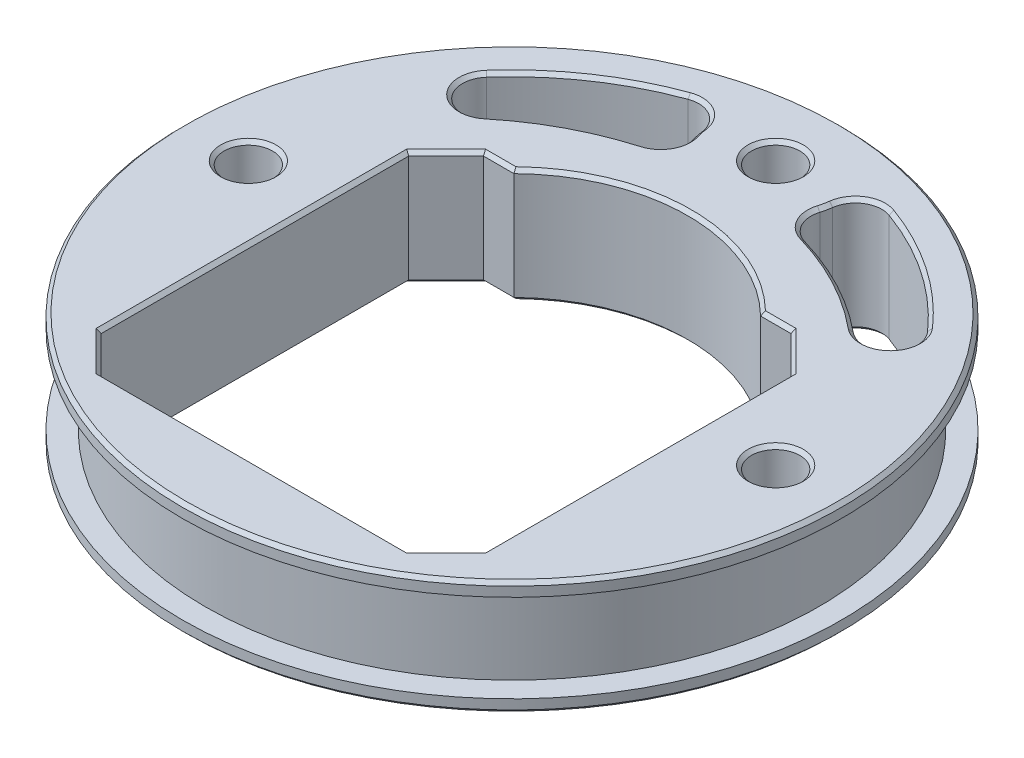
SolidWorks part; units mm, degrees
ref_plane "Front Plane" through (0, 0, 0) normal (0, 0, 1) x (1, 0, 0)
ref_plane "Top Plane" through (0, 0, 0) normal (0, 1, 0) x (1, 0, 0)
ref_plane "Right Plane" through (0, 0, 0) normal (1, 0, 0) x (0, 0, -1)
sketch "Sketch1" plane through (0, 0, 0) normal (0, 1, 0) x (1, 0, 0)
  line L0 (0, 0) -> (0, -7.5) construction
  line L1 (-17.4944, 14.25) -> (-14.0334, 14.25)
  line L2 (17.4944, 14.25) -> (21.75, 9.9944)
  line L3 (21.75, 9.9944) -> (21.75, -24.9944)
  line L4 (21.75, -24.9944) -> (17.4944, -29.25)
  line L5 (17.4944, -29.25) -> (-17.4944, -29.25)
  line L6 (-17.4944, -29.25) -> (-21.75, -24.9944)
  line L7 (-21.75, -24.9944) -> (-21.75, 9.9944)
  line L8 (-21.75, 9.9944) -> (-17.4944, 14.25)
  line L9 (14.0334, 14.25) -> (17.4944, 14.25)
  circle A0 centre (0, 0) radius 35 construction
  circle A1 centre (0, -7.5) radius 27.9127 construction
  circle A2 centre (0, 0) radius 30 construction
  circle A3 centre (0, 30) radius 2.75
  circle A4 centre (30, 0) radius 2.75
  circle A5 centre (-30, 0) radius 2.75
  circle A6 centre (0, 0) radius 37.5
  arc A7 (-20.9311, 17.8995) -> (20.9311, 17.8995) centre (0, -7.5) ccw construction
  arc A8 (7.1823, 27.8402) -> (7.4393, 29.0476) centre (0, 30) ccw
  arc A9 (6.9711, 32.7667) -> (-6.9711, 32.7667) centre (0, 0) ccw construction
  arc A10 (-25.0854, 22.203) -> (-20.9311, 17.8995) centre (-22.8389, 20.2147) ccw
  arc A11 (20.9311, 17.8995) -> (25.0854, 22.203) centre (22.8389, 20.2147) ccw
  arc A12 (-5.5389, 24.9433) -> (5.5389, 24.9433) centre (0, 30) ccw construction
  arc A13 (5.5389, 24.9433) -> (-5.5389, 24.9433) centre (0, -7.5) ccw construction
  arc A14 (-9.2152, 24.0963) -> (-20.9311, 17.8995) centre (0, -7.5) ccw
  arc A15 (20.9311, 17.8995) -> (9.2152, 24.0963) centre (0, -7.5) ccw
  arc A16 (25.0854, 22.203) -> (11.4394, 31.4863) centre (0, 0) ccw
  arc A17 (-11.4394, 31.4863) -> (-25.0854, 22.203) centre (0, 0) ccw
  arc A18 (-25.0854, 22.203) -> (25.0854, 22.203) centre (0, 0) ccw construction
  arc A19 (-7.4393, 29.0476) -> (-7.1823, 27.8402) centre (0, 30) ccw
  arc A20 (6.9711, 32.7667) -> (-6.9711, 32.7667) centre (0, 30) ccw construction
  arc A21 (11.4394, 31.4863) -> (7.4393, 29.0476) centre (10.415, 28.6667) ccw
  arc A22 (7.1823, 27.8402) -> (9.2152, 24.0963) centre (10.0552, 26.9763) ccw
  arc A23 (-9.2152, 24.0963) -> (-7.1823, 27.8402) centre (-10.0552, 26.9763) ccw
  arc A24 (-11.4394, 31.4863) -> (-7.4393, 29.0476) centre (-10.415, 28.6667) cw
  arc A25 (14.0334, 14.25) -> (-14.0334, 14.25) centre (0, 0) ccw
  dimension "D1" = 43.5
  dimension "D2" = 70
  dimension "D5" = 60
  dimension "D6" = 5.5
  dimension "D7" = 2.5
  dimension "D8" = 4
  dimension "D9" = 5
  dimension "D10" = 3
  dimension "D11" = 3
  dimension "D12" = 20
  dimension "D3" = 7.5
  dimension "D4" = 55.5
extrude "Boss-Extrude1" add sketch "Sketch1" along normal mid plane 13
sketch "Sketch2" plane through (0, 0, 0) normal (0, 1, 0) x (1, 0, 0)
  circle A0 centre (0, 0) radius 34.9
  dimension "D1" = 69.8
extrude "Cut-Extrude-Thin1" cut sketch "Sketch2" against normal mid plane 10 thin thin type one direction wall 10
chamfer "Chamfer1" distance 0.4 angle 45 2 edges at (0, -6.5, 37.5) (0, 6.5, 37.5)
chamfer "Chamfer2" distance 0.4 angle 45 50 edges at (-15.7639, -6.5, -14.25) (0, -6.5, -20) (15.7639, -6.5, -14.25) (19.6222, -6.5, -12.1222) (21.75, -6.5, 7.5) (19.6222, -6.5, 27.1222) (0, -6.5, 29.25) (-19.6222, -6.5, 27.1222) (-21.75, -6.5, 7.5) (-19.6222, -6.5, -12.1222) (30, -6.5, 2.75) (30, 6.5, 2.75) (-30, -6.5, 2.75) (-30, 6.5, 2.75) (0, -6.5, -27.25) (0, 6.5, -27.25) (-15.3883, 6.5, -21.5937) (-7.4188, 6.5, -25.5447) (-24.9973, 6.5, -18.1311) (-7.3357, 6.5, -28.4386) (-18.843, 6.5, -27.6982) (-8.8534, 6.5, -31.2282) (-15.3883, -6.5, -21.5937) (-7.4188, -6.5, -25.5447) (-24.9973, -6.5, -18.1311) (-7.3357, -6.5, -28.4386) (-18.843, -6.5, -27.6982) (-8.8534, -6.5, -31.2282) (7.4188, 6.5, -25.5447) (15.3883, 6.5, -21.5937) (7.3357, 6.5, -28.4386) (24.9973, 6.5, -18.1311) (8.8534, 6.5, -31.2282) (18.843, 6.5, -27.6982) (7.4188, -6.5, -25.5447) (15.3883, -6.5, -21.5937) (7.3357, -6.5, -28.4386) (24.9973, -6.5, -18.1311) (8.8534, -6.5, -31.2282) (18.843, -6.5, -27.6982) (15.7639, 6.5, -14.25) (19.6222, 6.5, -12.1222) (21.75, 6.5, 7.5) (19.6222, 6.5, 27.1222) (0, 6.5, 29.25) (-19.6222, 6.5, 27.1222) (-21.75, 6.5, 7.5) (-19.6222, 6.5, -12.1222) (0, 6.5, -20) (-15.7639, 6.5, -14.25)
